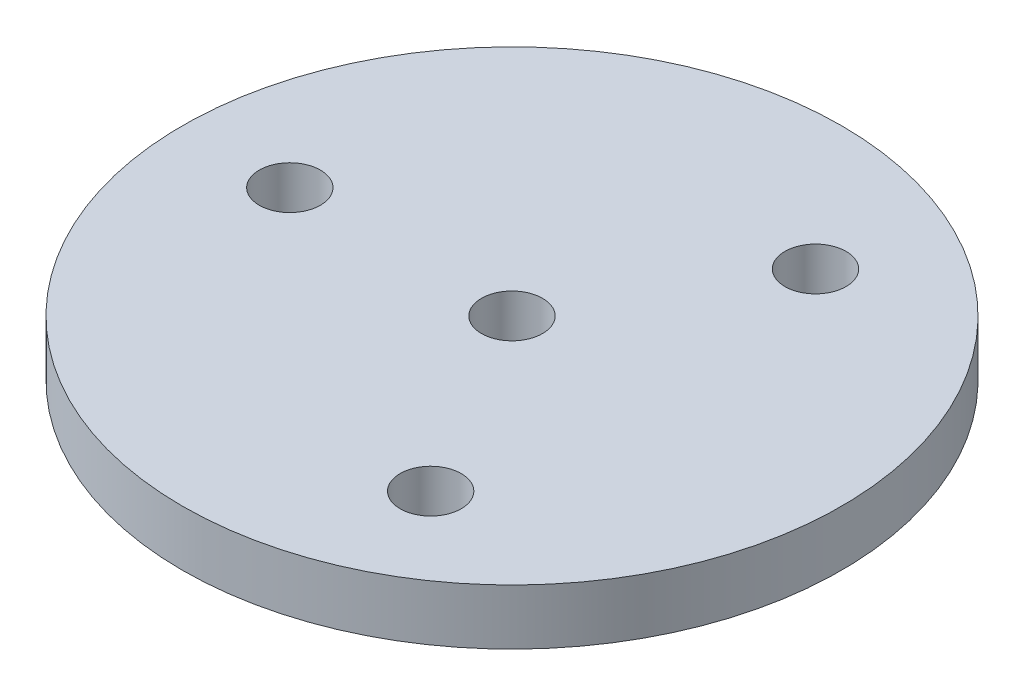
SolidWorks part; units mm, degrees
material "1.4301 (X5CrNi18-10)"
ref_plane "Vorne" through (0, 0, 0) normal (0, 0, 1) x (1, 0, 0)
ref_plane "Oben" through (0, 0, 0) normal (0, 1, 0) x (1, 0, 0)
ref_plane "Rechts" through (0, 0, 0) normal (1, 0, 0) x (0, 0, -1)
sketch "Skizze1" plane through (0, 0, 0) normal (1, 0, 0) x (0, 0, -1)
  line L0 (0, 0) -> (0, 4.7663) construction
  line L1 (-1, 0) -> (-17.8, 0)
  line L2 (-1, 0) -> (-1, 3)
  line L3 (-1, 3) -> (-17.8, 3)
  line L4 (-17.8, 0) -> (-17.8, 3)
  dimension "D1" = 3
  dimension "D2" = 1
  dimension "D3" = 17.8
revolve "Rotation1" add sketch "Skizze1" angle 360 about L0
sketch "Skizze2" plane through (0, 3, 0) normal (0, 1, 0) x (1, 0, 0)
  circle A0 centre (-12, 0) radius 1
  circle A1 centre (-12, 0) radius 3.5 construction
  dimension "D1" = 2
  dimension "D3" = 7
  dimension "D2" = 12
extrude "Schnitt-Linear austragen1" cut sketch "Skizze2" against normal through all
ref_axis "Achse1" through (0, 3, 0) along (0, -1, 0)
pattern_circular "Kreismuster1" count 3 over 360 about axis through (0, 3, 0) along (0, -1, 0) of "Schnitt-Linear austragen1"
hole_wizard "M4 Gewindebohrung1" positions "Skizze4" profile "Skizze3" tap size "M4" standard "DIN" end condition through all
sketch "Skizze4" plane through (0, 3, 0) normal (0, 1, 0) x (1, 0, 0)
  point P0 (0, 0)
  point P3 (6, 10.3923)
  point P6 (-12, 0)
  point P9 (6, -10.3923)
sketch "Skizze3" plane through (0, 3, 0) normal (1, 0, 0) x (0, 0, 1)
  line L0 (0, 0) -> (0, 3)
  line L1 (0, 3) -> (1.65, 3)
  line L2 (1.65, 3) -> (1.65, 0)
  line L5 (1.65, 0) -> (0, 0)
  line L11 (0, -6.35) -> (0, 107.95) construction
  dimension "Bohrerdurchmesser" = 3.3
  dimension "Bohrungstiefe" = 3
cosmetic thread "Bohrungsgewinde1" parameters "D2"=4
cosmetic thread "Bohrungsgewinde2" parameters "D2"=4
cosmetic thread "Bohrungsgewinde3" parameters "D2"=4
cosmetic thread "Bohrungsgewinde4" parameters "D2"=4
